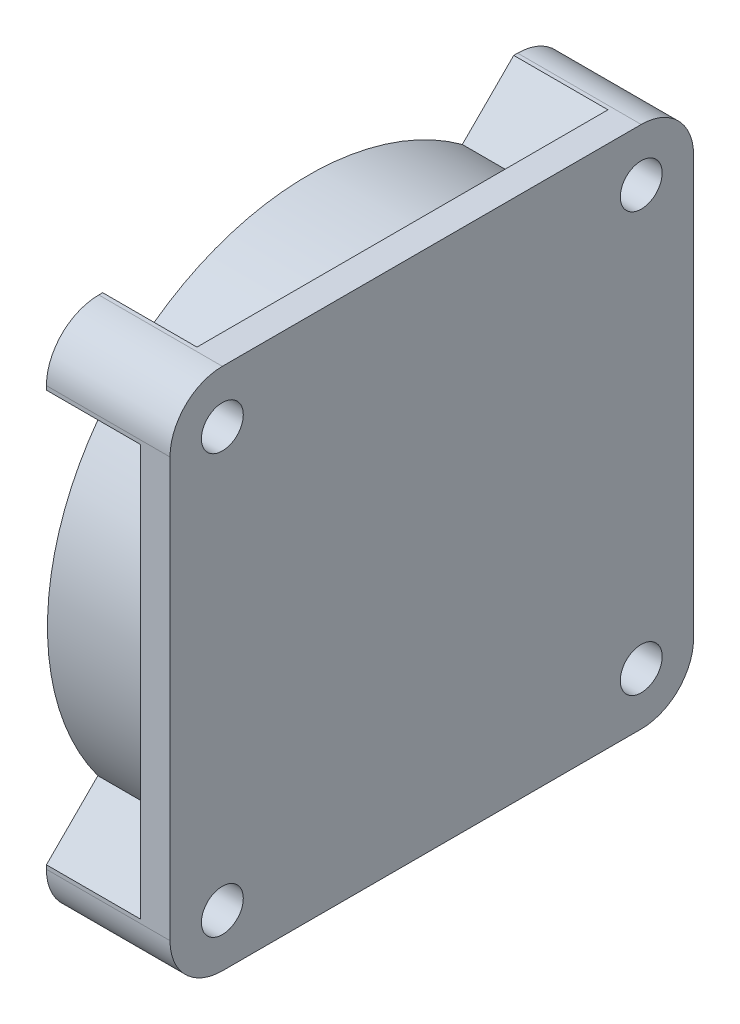
SolidWorks part; units mm, degrees
ref_plane "Front Plane" through (0, 0, 0) normal (0, 0, 1) x (1, 0, 0)
ref_plane "Top Plane" through (0, 0, 0) normal (0, 1, 0) x (1, 0, 0)
ref_plane "Right Plane" through (0, 0, 0) normal (1, 0, 0) x (0, 0, -1)
sketch "Sketch1" plane through (0, 0, 0) normal (1, 0, 0) x (0, 0, -1)
  line L0 (0, 0) -> (-20, -20) construction
  line L1 (-25, -25) -> (25, -25)
  line L2 (-25, -25) -> (-25, 25)
  line L3 (-25, 25) -> (25, 25)
  line L4 (25, -25) -> (25, 25)
  line L5 (-25, -25) -> (25, 25) construction
  line L6 (-25, 25) -> (25, -25) construction
  line L7 (0, 0) -> (-20, 20) construction
  line L8 (-95.2582, -24.3247) -> (94.7418, -24.3247) construction
  line L9 (-95.2582, 24.7533) -> (94.7418, 24.7533) construction
  circle A0 centre (-20, -20) radius 2
  circle A1 centre (-20, 20) radius 2
  circle A2 centre (20, 20) radius 2
  circle A3 centre (20, -20) radius 2
  point P0 (0, 0)
  dimension "D2" = 4
  dimension "D1" = 50
  dimension "D3" = 5
  dimension "D5" = 90
  dimension "D4" = 4
extrude "Body" add sketch "Sketch1" along normal blind 11.8
fillet "Fillet1" radius 5 4 edges at (5.9, 25, -25) (5.9, -25, -25) (5.9, -25, 25) (5.9, 25, 25)
sketch "Sketch2" plane through (0, 0, 0) normal (-1, 0, 0) x (0, 0, 1)
  line L0 (0, 0) -> (-20, -20) construction
  line L1 (0, 0) -> (-20, 20) construction
  circle A0 centre (-20, -20) radius 3.05
  circle A1 centre (-20, 20) radius 3.05
  circle A2 centre (20, 20) radius 3.05
  circle A3 centre (20, -20) radius 3.05
  dimension "D1" = 6.1
  dimension "D3" = 90
  dimension "D2" = 4
extrude "C'Bores" cut sketch "Sketch2" against normal blind 1.5
sketch "Sketch3" plane through (0, 0, 0) normal (-1, 0, 0) x (0, 0, 1)
  line L0 (-20, -20) -> (8.7189, 8.7189) construction
  line L1 (-25, -19.626) -> (-20.0877, -14.7137)
  line L3 (-19.626, -25) -> (-14.7137, -20.0877)
  line L7 (-19.626, 25) -> (-14.7137, 20.0877)
  line L8 (-25, 19.626) -> (-20.0877, 14.7137)
  line L9 (25, 19.626) -> (20.0877, 14.7137)
  line L10 (19.626, 25) -> (14.7137, 20.0877)
  line L11 (19.626, -25) -> (14.7137, -20.0877)
  line L12 (25, -19.626) -> (20.0877, -14.7137)
  line L13 (0, 0) -> (-16.7809, -11.4069) construction
  line L14 (0, 0) -> (-11.4069, 16.7809) construction
  line L15 (25, 20) -> (25, -20) construction
  line L16 (-20, 25) -> (20, 25) construction
  line L17 (-25, -20) -> (-25, 20) construction
  line L18 (20, -25) -> (-20, -25) construction
  line L19 (25, 19.626) -> (25, -19.626)
  line L20 (-19.626, 25) -> (19.626, 25)
  line L21 (-25, -19.626) -> (-25, 19.626)
  line L22 (19.626, -25) -> (-19.626, -25)
  arc A1 (20.0877, -14.7137) -> (20.0877, 14.7137) centre (0, 0) ccw
  arc A2 (-14.7137, -20.0877) -> (14.7137, -20.0877) centre (0, 0) ccw
  arc A3 (-20.0877, 14.7137) -> (-20.0877, -14.7137) centre (0, 0) ccw
  arc A4 (14.7137, 20.0877) -> (-14.7137, 20.0877) centre (0, 0) ccw
  dimension "D2" = 90
  dimension "D3" = 49.8
  dimension "D1" = 7.6
extrude "Cut-Extrude1" cut sketch "Sketch3" against normal offset from surface (9 mm away) 2.8 up to face at (11.8, 0, 0)
other "CPoint1" parameters "Diameter"=2, "StubLength"=3
ref_axis "Axis1" through (9, 19.626, 35) along (0, 0, -1)
